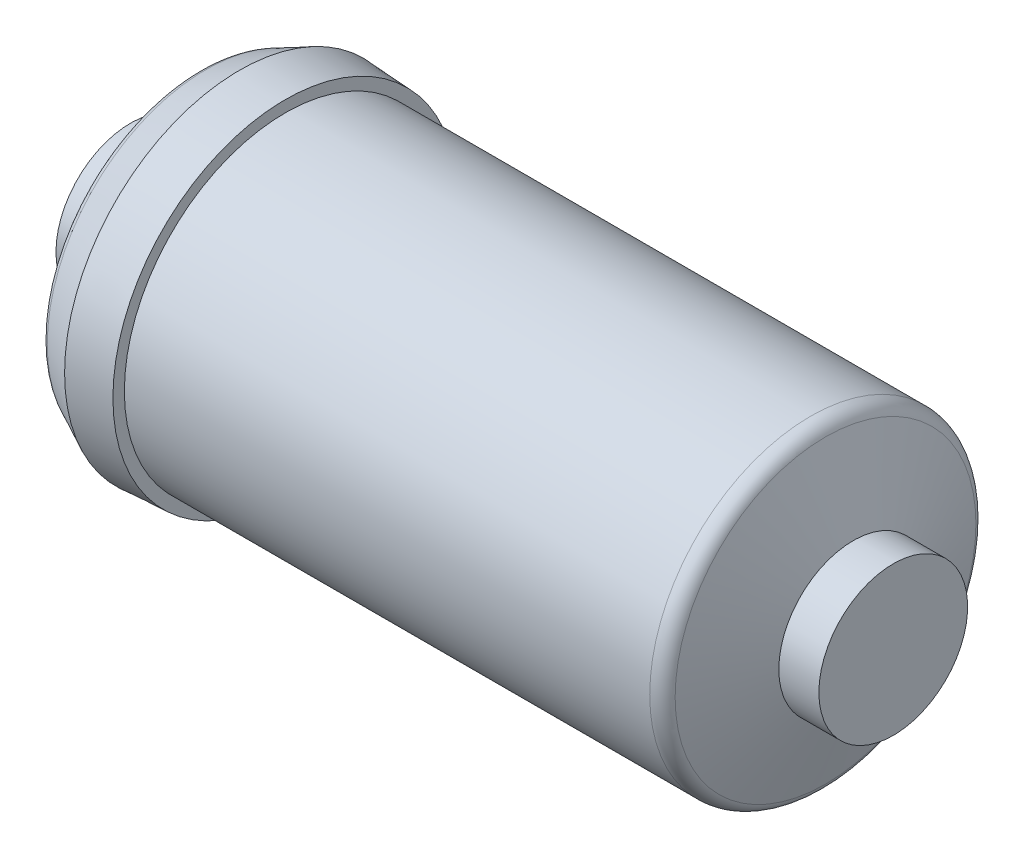
SolidWorks part; units mm, degrees
ref_plane "Front Plane" through (0, 0, 0) normal (0, 0, 1) x (1, 0, 0)
ref_plane "Top Plane" through (0, 0, 0) normal (0, 1, 0) x (1, 0, 0)
ref_plane "Right Plane" through (0, 0, 0) normal (1, 0, 0) x (0, 0, -1)
sketch "Sketch1" plane through (0, 0, 0) normal (0, 0, 1) x (1, 0, 0)
  line L0 (0, 0) -> (152.4, 0) construction
  line L1 (0, 0) -> (0, 14.859)
  line L2 (0, 14.859) -> (8.001, 14.859)
  line L3 (8.001, 14.859) -> (13.9177, 31.115)
  line L4 (13.9177, 31.115) -> (21.7917, 34.925)
  line L5 (21.7917, 34.925) -> (30.9357, 34.417)
  line L6 (30.9357, 34.417) -> (30.9357, 32.131)
  line L7 (30.9357, 32.131) -> (138.1125, 32.131)
  line L8 (138.1125, 32.131) -> (144.399, 14.859)
  line L9 (144.399, 14.859) -> (152.4, 14.859)
  line L10 (152.4, 14.859) -> (152.4, 0)
  line L11 (0, 0) -> (152.4, 0)
  dimension "D1" = 64.262
  dimension "D2" = 69.85
  dimension "D3" = 2.286
  dimension "D4" = 29.718
  dimension "D5" = 8.001
  dimension "D6" = 110
  dimension "D7" = 62.23
  dimension "D8" = 110
  dimension "D9" = 152.4
  dimension "D10" = 17.018
  dimension "D11" = 9.144
revolve "Revolve1" add sketch "Sketch1" angle 360 about L0
fillet "Fillet1" radius 3.175 2 edges at (138.1125, 0, 32.131) (13.9177, 0, 31.115)
